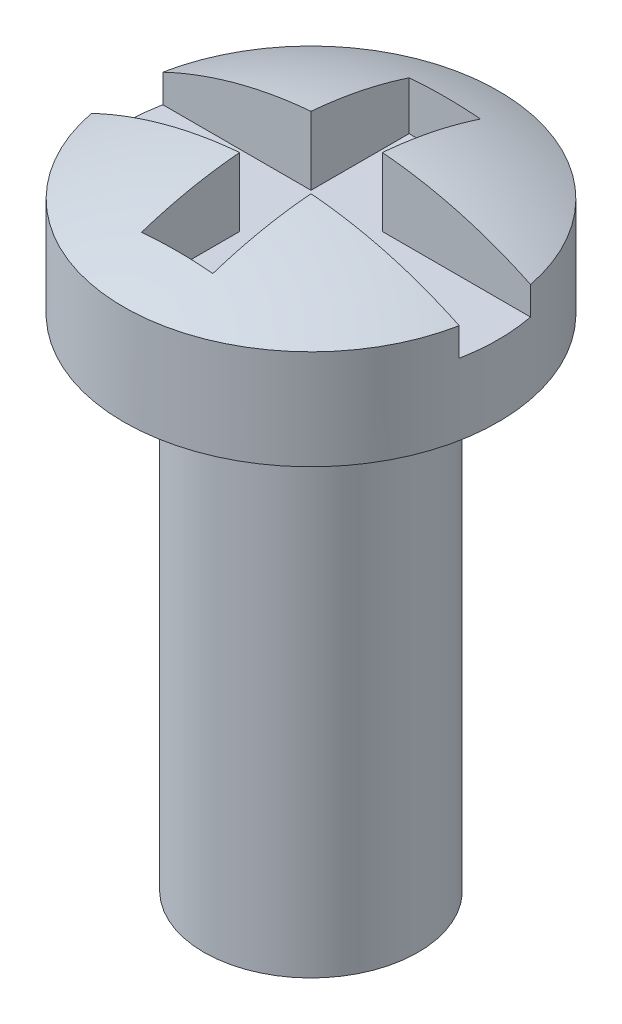
SolidWorks part; units mm, degrees
ref_plane "前视基准面" through (0, 0, 0) normal (0, 0, 1) x (1, 0, 0)
ref_plane "上视基准面" through (0, 0, 0) normal (0, 1, 0) x (1, 0, 0)
ref_plane "右视基准面" through (0, 0, 0) normal (1, 0, 0) x (0, 0, -1)
sketch "草图1" plane through (0, 0, 0) normal (0, 1, 0) x (1, 0, 0)
  circle A0 centre (0, 0) radius 1.5
  dimension "D1" = 3
extrude "拉伸1" add sketch "草图1" along normal blind 7
sketch "草图2" plane through (0, 7, 0) normal (0, 1, 0) x (-1, 0, 0)
  circle A0 centre (0, 0) radius 2.625
  dimension "D1" = 5.25
extrude "拉伸2" add sketch "草图2" along normal blind 2
sketch "草图3" plane through (0, 9, 0) normal (0, 1, 0) x (-1, 0, 0)
  line L0 (4.0624, 0) -> (-4.2778, 0) construction
  line L1 (0, -3.5166) -> (0, 3.738) construction
  line L3 (3.5023, -0.5) -> (-3.5023, -0.5)
  line L4 (3.5023, -0.5) -> (3.5023, 0.5)
  line L5 (3.5023, 0.5) -> (-3.5023, 0.5)
  line L6 (-3.5023, -0.5) -> (-3.5023, 0.5)
  dimension "D1" = 1
extrude "切除-拉伸1" cut sketch "草图3" against normal blind 1
sketch "草图4" plane through (0, 9, 0) normal (0, 1, 0) x (-1, 0, 0)
  line L0 (0, -3.8639) -> (0, 3.6765) construction
  line L1 (1.7727, 0) -> (-1.7019, 0) construction
  line L2 (0.5, -1.875) -> (-0.5, -1.875)
  line L3 (0.5, -1.875) -> (0.5, 1.875)
  line L4 (0.5, 1.875) -> (-0.5, 1.875)
  line L5 (-0.5, -1.875) -> (-0.5, 1.875)
  dimension "D1" = 1
  dimension "D2" = 3.75
extrude "切除-拉伸2" cut sketch "草图4" against normal blind 1
sketch "草图5" plane through (0, 0, 0) normal (1, 0, 0) x (0, 0, -1)
  line L0 (0, -2.1059) -> (0, 12.2815) construction
  line L1 (-0.5, 9) -> (-2.625, 9) construction
  line L2 (0, 10.9998) -> (-4.5494, 10.9998)
  line L3 (-4.5494, 6.9119) -> (-4.5494, 10.9998)
  line L5 (0, 10.9998) -> (0, 9)
  arc A2 (0, 9) -> (-4.5494, 6.9119) centre (0, 3) ccw
  dimension "D1" = 6
revolve "切除-旋转16" cut sketch "草图5" angle 360 about L0
